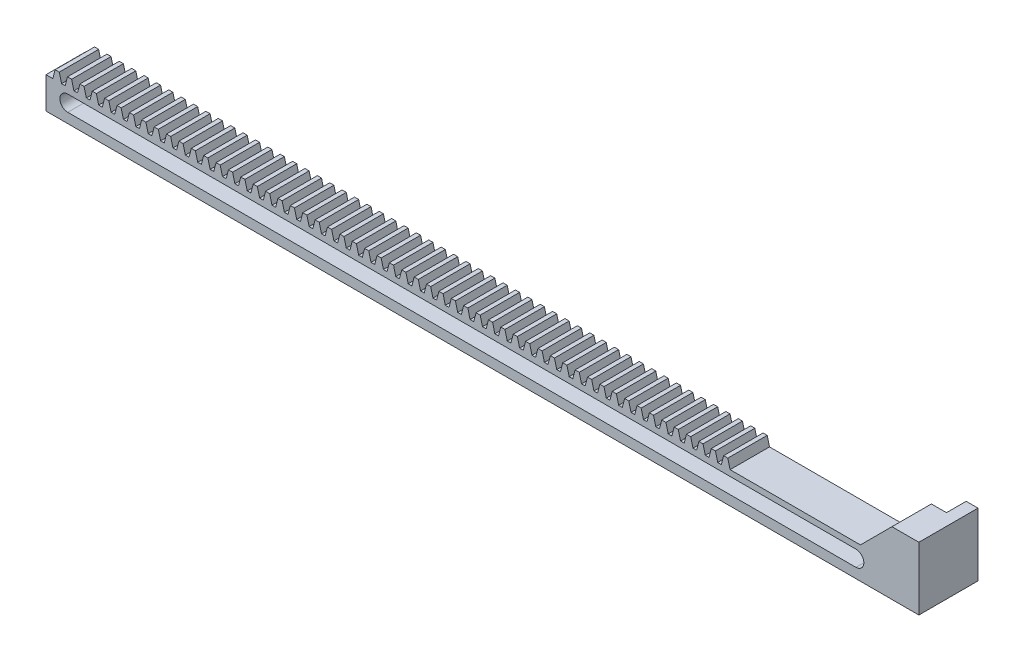
SolidWorks part; units mm, degrees
material "1.1193 (C45G)"
ref_plane "Front" through (0, 0, 0) normal (0, 0, 1) x (1, 0, 0)
ref_plane "Top" through (0, 0, 0) normal (0, 1, 0) x (1, 0, 0)
ref_plane "Right" through (0, 0, 0) normal (1, 0, 0) x (0, 0, -1)
sketch "Sketch1" plane through (0, 0, 0) normal (0, 0, 1) x (1, 0, 0)
  line L1 (0, 0) -> (188.4956, 0)
  line L2 (0, 0) -> (0, -8)
  line L3 (0, -8) -> (188.4956, -8)
  line L4 (188.4956, 0) -> (188.4956, -8)
  dimension "D1" = 8
  dimension "L" = 188.4956
extrude "Extrude1" add sketch "Sketch1" along normal blind 10
sketch "草图5" plane through (0, 0, 0) normal (-1, 0, 0) x (0, 0, 1)
  line L4 (0, 0) -> (0, -8)
  line L5 (0, -8) -> (10, -8)
  line L6 (10, -8) -> (10, 0)
  line L7 (10, 0) -> (0, 0)
  line L8 (0, 0) -> (0, -8)
  line L9 (0, -8) -> (10, -8)
  line L10 (10, -8) -> (10, 0)
  line L12 (10, 0) -> (0, 0)
  dimension "D1" = 0
extrude "凸台-拉伸1" add sketch "草图5" along normal blind 30
sketch "Sketch2" plane through (0, 0, 10) normal (0, 0, 1) x (1, 0, 0)
  line L0 (0, 0) -> (0.5819, 2.25)
  line L1 (0.5819, 2.25) -> (1.6355, 2.25)
  line L2 (1.6355, 2.25) -> (2.2173, 0)
  line L3 (188.4956, 0) -> (-30, 0) construction
  line L4 (0, 0) -> (2.2173, 0)
  line L5 (0.3233, 1.25) -> (1.8941, 1.25) construction
  dimension "alpha2" = 75.5
  dimension "alpha" = 104.5
  dimension "ha" = 1
  dimension "hf" = 1.25
  dimension "S" = 1.5708
extrude "Extrude2" add sketch "Sketch2" against normal up to surface (10 mm away) up to face at (79.2478, -4, 0)
pattern_linear "LPattern1" count 10 spacing 3.1415 along (-1, 0, 0) of "Extrude2" pattern seed only yes
sketch "草图2" plane through (0, 0, 10) normal (0, 0, 1) x (1, 0, 0)
  line L0 (-15.5044, -3.5) -> (193.7496, -3.5) construction
  line L1 (-24.4808, -3.5) -> (175.5192, -3.5) construction
  line L2 (-24.4808, -1.5) -> (175.5192, -1.5)
  line L3 (-24.4808, -5.5) -> (175.5192, -5.5)
  arc A0 (-24.4808, -1.5) -> (-24.4808, -5.5) centre (-24.4808, -3.5) ccw
  arc A1 (175.5192, -5.5) -> (175.5192, -1.5) centre (175.5192, -3.5) ccw
  point P5 (75.5192, -3.5)
  dimension "D1" = 2
  dimension "D2" = 200
extrude "切除-拉伸1" cut sketch "草图2" against normal blind 6
sketch "草图3" plane through (0, 0, 4) normal (0, 0, 1) x (1, 0, 0)
  line L0 (-24.4808, -3.5) -> (175.5192, -3.5) construction
  line L1 (-24.4808, -1.5) -> (175.5192, -1.5)
  line L2 (-24.4808, -5.5) -> (175.5192, -5.5)
  arc A0 (-24.4808, -1.5) -> (-24.4808, -5.5) centre (-24.4808, -3.5) ccw
  arc A1 (175.5192, -5.5) -> (175.5192, -1.5) centre (175.5192, -3.5) ccw
  point P4 (75.5192, -3.5)
  dimension "D1" = 2
extrude "切除-拉伸2" cut sketch "草图3" against normal blind 6
fillet "圆角1" [suppressed] radius 5
sketch "草图8" plane through (188.4956, 0, 0) normal (1, 0, 0) x (0, 0, -1)
  line L0 (-10, -8) -> (0, -8) construction
  line L1 (-10, 0) -> (5, 0)
  line L2 (-10, 0) -> (-10, -8)
  line L3 (-10, -8) -> (5, -8)
  line L4 (5, 0) -> (5, -8)
  dimension "D1" = 15
extrude "凸台-拉伸2" add sketch "草图8" along normal blind 3
sketch "草图9" plane through (0, 0, 0) normal (0, 1, 0) x (1, 0, 0)
  line L6 (186.6597, 0) -> (186.6597, -10)
  line L12 (188.4956, 0) -> (143.589, 0)
  line L13 (143.589, 0) -> (143.589, -10)
  line L14 (143.589, -10) -> (191.4956, -10)
  line L15 (191.4956, -10) -> (191.4956, 5)
  line L16 (191.4956, 5) -> (188.4956, 5)
  line L17 (188.4956, 5) -> (188.4956, 0)
  line L18 (188.4956, 0) -> (143.589, 0)
  line L19 (143.589, 0) -> (143.589, -10)
  line L20 (143.589, -10) -> (191.4956, -10)
  line L21 (191.4956, -10) -> (191.4956, 5)
  line L22 (191.4956, 5) -> (188.4956, 5)
  line L23 (188.4956, 5) -> (188.4956, 0)
  line M7 (188.4956, 0) -> (143.589, 0)
  line M9 (143.589, -10) -> (191.4956, -10)
  line M10 (191.4956, -10) -> (191.4956, 5)
  line M11 (191.4956, 5) -> (188.4956, 5)
  line M12 (188.4956, 5) -> (188.4956, 0)
  dimension "D1" = 0
extrude "凸台-拉伸3" add sketch "草图9" along normal blind 8 contours L6 M7 M9 M10 M11 M12 region at (189.2949, 0, 3.2244)
chamfer "倒角1" distance 10 angle 45 1 edges at (186.6597, 0, 5)
